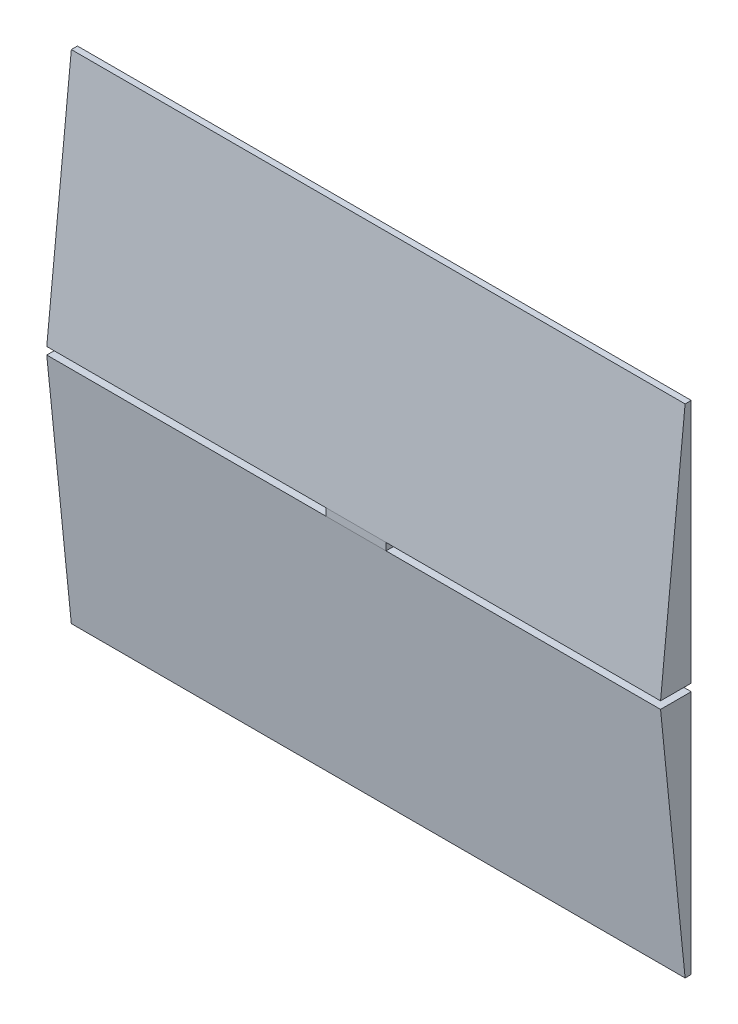
SolidWorks part; units mm, degrees
ref_plane "Płaszczyzna przednia" through (0, 0, 0) normal (0, 0, 1) x (1, 0, 0)
ref_plane "Płaszczyzna górna" through (0, 0, 0) normal (0, 1, 0) x (1, 0, 0)
ref_plane "Płaszczyzna prawa" through (0, 0, 0) normal (1, 0, 0) x (0, 0, -1)
sketch "Szkic1" plane through (0, 0, 0) normal (0, 0, 1) x (1, 0, 0)
  line L1 (-29.6834, 11.2149) -> (70.3166, 11.2149)
  line L2 (-29.6834, 11.2149) -> (-29.6834, -28.6851)
  line L3 (-29.6834, -28.6851) -> (70.3166, -28.6851)
  line L4 (70.3166, 11.2149) -> (70.3166, -28.6851)
  line L8 (25.5908, 11.2149) -> (25.5908, 11.8149)
  line L9 (25.5908, 11.8149) -> (15.7908, 11.8149)
  line L10 (15.7908, 11.8149) -> (15.7908, 11.2149)
  line L11 (15.7908, 11.2149) -> (25.5908, 11.2149)
extrude "Dodanie-wyciągnięcie1" add sketch "Szkic1" along normal blind 1 contours L4 L1 L2 L3 | L9 L10 L11 L8 region at (20.3166, -8.7351, 0)
sketch "Szkic2" plane through (-29.6834, 0, 0) normal (-1, 0, 0) x (0, 0, 1)
  line L0 (1, 11.2149) -> (5, 11.2149)
  line L1 (5, 11.2149) -> (1, -28.6851)
  line L2 (1, -28.6851) -> (1, 11.2149)
extrude "Dodanie-wyciągnięcie2" add sketch "Szkic2" against normal blind 100
extrude "Dodanie-wyciągnięcie3" add sketch "Szkic1<3>" along normal blind 5 contours L9 L10 L11 L8
sketch "Szkic1<3>" plane through (0, 0, 0) normal (0, 0, 1) x (1, 0, 0) same geometry as "Szkic1"
mirror "Lustro1" about plane through (25.5908, 11.8149, 1) normal (0, -1, 0) of bodies 103
